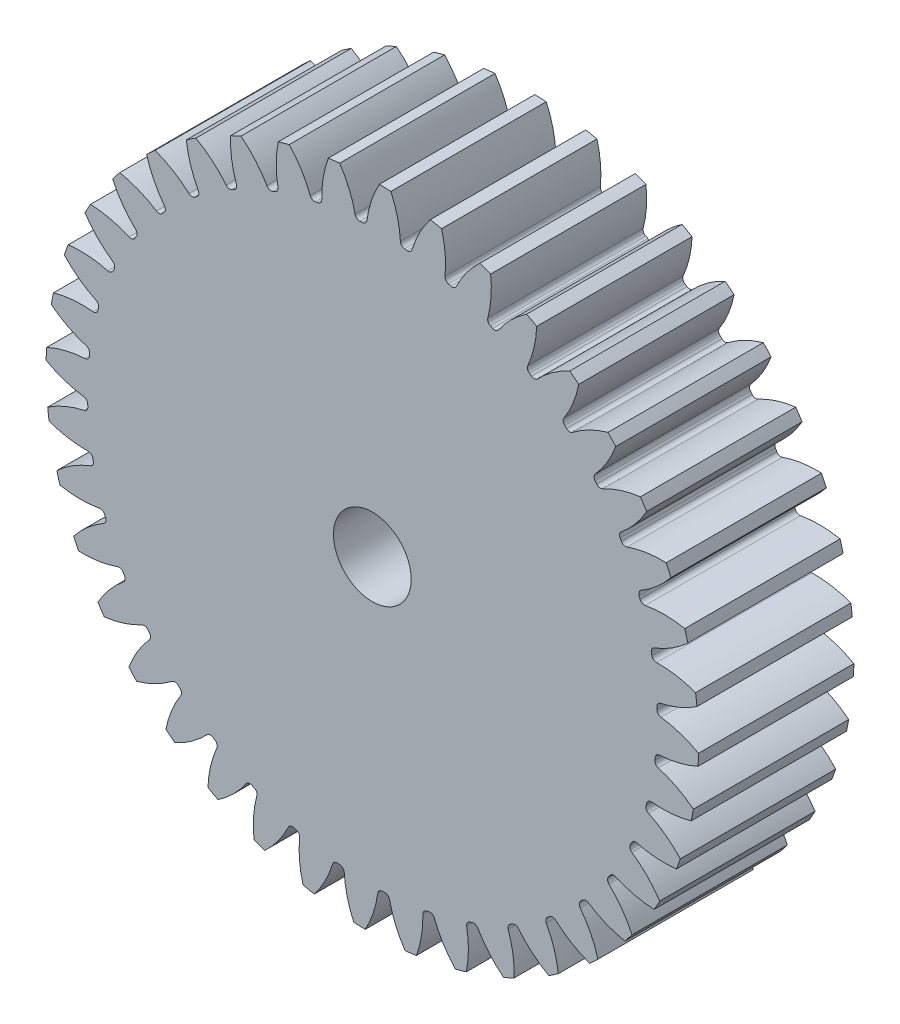
SolidWorks part; units mm, degrees
material "PA Tipo 6"
ref_plane "Front Plane" through (0, 0, 0) normal (0, 0, 1) x (1, 0, 0)
ref_plane "Top Plane" through (0, 0, 0) normal (0, 1, 0) x (1, 0, 0)
ref_plane "Right Plane" through (0, 0, 0) normal (1, 0, 0) x (0, 0, -1)
sketch "Croquis1" plane through (0, 0, 0) normal (0, 0, 1) x (1, 0, 0)
  line L0 (0, 0) -> (0, 111.7136) construction
  line L1 (0, 20) -> (6.428, 17.6603) construction
  line L2 (0, 0) -> (4.6352, 118.004) construction
  line L3 (1.5688, 19.9384) -> (-5.0229, 18.1101) construction
  circle A0 centre (0, 0) radius 18.7938 construction
  circle A1 centre (0, 0) radius 18.33 construction
  circle A2 centre (0, 0) radius 20 construction
  circle A3 centre (0, 0) radius 21 construction
  arc A4 (0.4553, 20.9951) -> (-0.3801, 18.3261) centre (6.428, 17.6603) ccw
  arc A5 (1.1929, 20.9661) -> (1.8164, 18.2398) centre (-5.0229, 18.1101) cw
  dimension "De" = 42
  dimension "Dp" = 40
  dimension "Dt" = 36.66
  dimension "ct" = 37.5876
  dimension "Ed" = 1.57
sketch "Croquis2" plane through (0, 0, 0) normal (0, 0, 1) x (1, 0, 0)
  circle A0 centre (0, 0) radius 18.33 construction
  circle A1 centre (0, 0) radius 21 construction
  arc A2 (0.4553, 20.9951) -> (-0.3801, 18.3261) centre (6.428, 17.6603) ccw construction
  arc A3 (1.8164, 18.2398) -> (1.1929, 20.9661) centre (-5.0229, 18.1101) ccw construction
  arc A4 (-0.3801, 18.3261) -> (1.8164, 18.2398) centre (0, 0) ccw
  arc A5 (1.1929, 20.9661) -> (0.4553, 20.9951) centre (0, 0) ccw
  arc A6 (0.4553, 20.9951) -> (-0.3801, 18.3261) centre (6.428, 17.6603) ccw
  arc A7 (1.8164, 18.2398) -> (1.1929, 20.9661) centre (-5.0229, 18.1101) ccw
extrude "Saliente-Extruir1" add sketch "Croquis2" along normal blind 10
fillet "Redondeo1" radius 0.3 2 edges at (-0.3801, 18.3261, 5) (1.8164, 18.2398, 5)
pattern_circular "MatrizC1" count 40 over 360 about axis through (0, 0, 10) along (0, 0, 1) of "Saliente-Extruir1", "Redondeo1"
sketch "Croquis3" plane through (0, 0, 10) normal (0, 0, 1) x (1, 0, 0)
  circle A0 centre (0, 0) radius 2.5
  dimension "D1" = 5
extrude "Cortar-Extruir1" cut sketch "Croquis3" against normal through all
ref_axis "Eje1" through (0, 0, 104.6592) along (0, 0, -1)
equation "\"M\"= 1"
equation "\"N\"= 40"
equation "\"a\"= 20"
equation "\"De@Croquis1\"= \"M\" * ( \"N\" + 2 )"
equation "\"Dp@Croquis1\" = \"M\" * \"N\""
equation "\"Dt@Croquis1\"= \"Dp@Croquis1\" - ( \"M\" * 2 * 1.67 )"
equation "\"ct@Croquis1\"= \"Dp@Croquis1\" * 0.93969"
equation "\"Ed@Croquis1\"= \"M\" * 1.57"
equation "\"r@Redondeo1\"= \"M\" * 0.3"
equation "\"D1@MatrizC1\"=\"N\""
